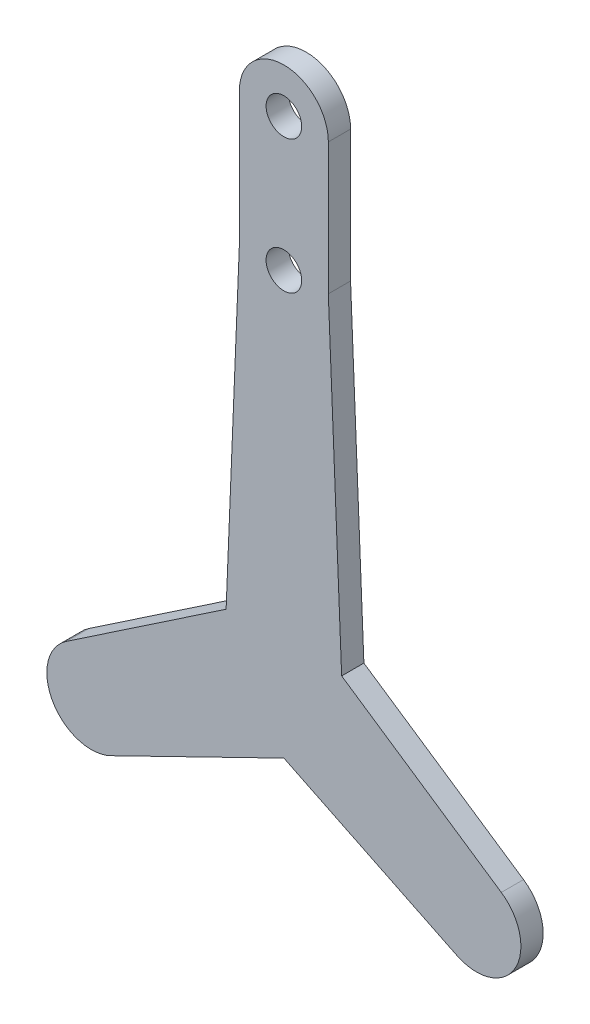
SolidWorks part; units mm, degrees
ref_plane "Front Plane" through (0, 0, 0) normal (0, 0, 1) x (1, 0, 0)
ref_plane "Top Plane" through (0, 0, 0) normal (0, 1, 0) x (1, 0, 0)
ref_plane "Right Plane" through (0, 0, 0) normal (1, 0, 0) x (0, 0, -1)
ref_axis "X" through (-88.99, 0, 0) along (1, 0, 0)
ref_axis "Y" through (0, 55, 0) along (0, -1, 0)
ref_axis "Z" through (0, 0, -88.99) along (0, 0, 1)
sketch "Sketch1" plane through (0, 0, 0) normal (0, 0, 1) x (1, 0, 0)
  line L0 (0, 0) -> (0, -80) construction
  line L1 (0, -80) -> (-43.3013, -105) construction
  line L2 (0, -80) -> (43.3013, -105) construction
  line L3 (0, -80) -> (-12.9904, -72.5) construction
  line L4 (-38.9163, -113.9873) -> (0, -95)
  line L5 (0, -95) -> (38.9163, -113.9873)
  line L6 (-12.9904, -72.5) -> (0, -80) construction
  line L7 (0, -80) -> (12.9904, -72.5) construction
  line L8 (-12.9904, -72.5) -> (-48.8921, -96.7089)
  line L9 (48.8921, -96.7089) -> (12.9904, -72.5)
  line L10 (-12.9904, -72.5) -> (-9.9916, 0.411)
  line L11 (12.9904, -72.5) -> (9.9916, 0.411)
  line L12 (0, 0) -> (0, 30) construction
  line L13 (-10, 30) -> (-9.9916, 0.411)
  line L14 (10, 30) -> (9.9916, 0.411)
  circle A0 centre (-43.3013, -105) radius 10 construction
  circle A1 centre (43.3013, -105) radius 10 construction
  circle A2 centre (0, -80) radius 15 construction
  circle A3 centre (0, 0) radius 10 construction
  arc A4 (-48.8921, -96.7089) -> (-38.9163, -113.9873) centre (-43.3013, -105) ccw
  arc A5 (48.8921, -96.7089) -> (38.9163, -113.9873) centre (43.3013, -105) cw
  circle A7 centre (0, 30) radius 10 construction
  arc A8 (-10, 30) -> (10, 30) centre (0, 30) cw
  dimension "D6" = 20
  dimension "D7" = 20
  dimension "D8" = 30
  dimension "D9" = 20
  dimension "D13" = 20
  dimension "D1" = 80
  dimension "D2" = 50
  dimension "D3" = 50
  dimension "D4" = 120
  dimension "D5" = 120
  dimension "D10" = 60
  dimension "D11" = 60
  dimension "D12" = 30
extrude "Boss-Extrude1" add sketch "Sketch1" along normal blind 5 contours L11 L14 A8 L13 L10 L8 A4 L4 L5 A5 L9
sketch "Sketch3" plane through (0, 0, 0) normal (0, 0, -1) x (-1, 0, 0)
  circle A0 centre (0, 30) radius 4
  circle A1 centre (0, 0) radius 4
  dimension "D1" = 8
  dimension "D2" = 8
extrude "Cut-Extrude1" cut sketch "Sketch3" against normal blind 5
